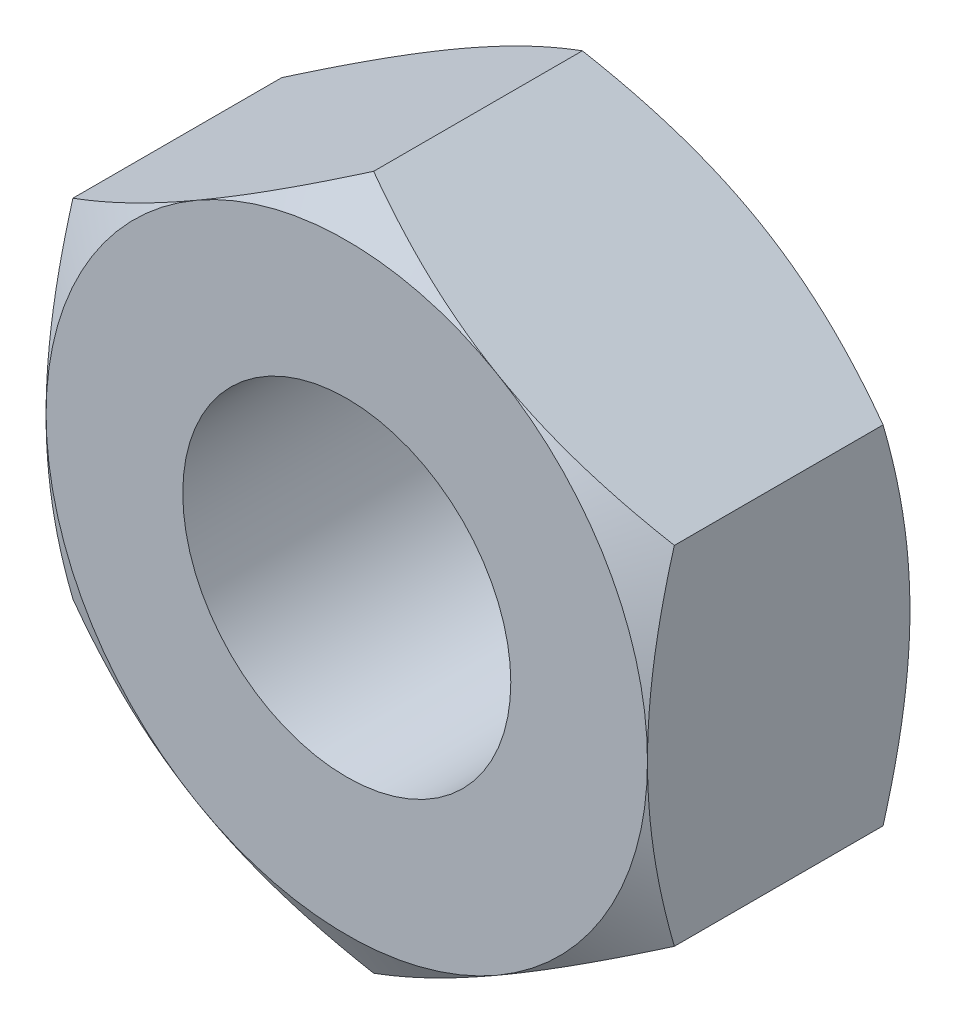
SolidWorks part; units mm, degrees
material "AISI 304"
ref_plane "Front" through (0, 0, 0) normal (0, 0, 1) x (1, 0, 0)
ref_plane "Top" through (0, 0, 0) normal (0, 1, 0) x (1, 0, 0)
ref_plane "Right" through (0, 0, 0) normal (1, 0, 0) x (0, 0, -1)
sketch "Sketch1" plane through (0, 0, 0) normal (0, 0, 1) x (1, 0, 0)
  line L1 (-2.75, 1.5877) -> (-2.75, -1.5877)
  line L2 (-2.75, -1.5877) -> (0, -3.1754)
  line L3 (0, -3.1754) -> (2.75, -1.5877)
  line L4 (2.75, -1.5877) -> (2.75, 1.5877)
  line L5 (2.75, 1.5877) -> (0, 3.1754)
  line L6 (0, 3.1754) -> (-2.75, 1.5877)
  circle A0 centre (0, 0) radius 2.75 construction
  circle A1 centre (0, 0) radius 1.5 construction
  point P10 (0, 1.5)
  dimension "hex" = 5.5
  dimension "dia" = 3
extrude "Extrude1" add sketch "Sketch1" along normal mid plane 2.4
sketch "Sketch4" plane through (0, 0, -1.2) normal (0, 0, -1) x (-1, 0, 0)
  circle A0 centre (0, 0) radius 1.5 construction
  circle A1 centre (0, 0) radius 1.5
sketch "Sketch10" plane through (0, 0, 1.2) normal (0, 0, 1) x (1, 0, 0)
  circle A0 centre (0, 0) radius 1.5 construction
  circle A1 centre (0, 0) radius 1.5
extrude "Cut-Extrude2" cut sketch "Sketch10" against normal through all draft 45
sketch "Sketch11" plane through (0, 0, -1.2) normal (0, 0, -1) x (-1, 0, 0)
  circle A0 centre (0, 0) radius 1.5 construction
  circle A1 centre (0, 0) radius 1.5
extrude "Cut-Extrude3" cut sketch "Sketch11" against normal through all draft 45
sketch "Sketch13" plane through (0, 0, -1.2) normal (0, 0, -1) x (-1, 0, 0)
  circle A0 centre (0, 0) radius 1.5 construction
  circle A1 centre (0, 0) radius 1.5
extrude "Boss-Extrude1" add sketch "Sketch13" against normal up to vertex (2.4 mm away) separate body up to point (-2.75, 1.5877, 1.2)
curve "Helix/Spiral3" pitch 0.5 height 2.4 turns 4.8
sketch "Sketch12" plane through (0, 0, 0) normal (1, 0, 0) x (0, 0, -1)
  line L0 (1.6375, 1.5) -> (1.2, 1.5)
  line L1 (1.6375, 1.5) -> (1.45, 1.1752)
  line L2 (1.45, 1.1752) -> (1.3875, 1.1752)
  line L3 (1.3875, 1.1752) -> (1.2, 1.5)
  line L4 (1.4187, 1.1752) -> (1.4187, 1.5) construction
  line L5 (1.2937, 1.3376) -> (1.5437, 1.3376) construction
  dimension "D1" = 60
  dimension "D2" = 0.0625
  dimension "D3" = 0.25
sweep "Cut-Sweep1" [suppressed] cut profiles "Sketch12" path "Helix/Spiral3"
combine bodies "Combine1" operation type subtract main body 116 bodies to subtract 117
sketch "Sketch7" plane through (0, 0, 1.2) normal (0, 0, 1) x (1, 0, 0)
  circle A0 centre (0, 0) radius 2.75 construction
  circle A1 centre (0, 0) radius 2.75
extrude "Extrude2" cut sketch "Sketch7" against normal blind 25.4 draft 60 flip side to cut
mirror "Mirror2" about plane through (0, 0, 0) normal (0, 0, 1) of "Extrude2"
sketch "Sketch8" plane through (0, 0, 1.2) normal (0, 0, 1) x (1, 0, 0)
  line L0 (-1.0607, 1.0607) -> (0, 0) construction
  line L1 (0, -1.5313) -> (0, 1.5313) construction
  circle A1 centre (0, 0) radius 1.5 construction
  point P0 (-1.0607, 1.0607)
  dimension "D1" = 45
sketch "Sketch14" plane through (0, 0, 1.2) normal (0, 0, 1) x (1, 0, 0)
  line L0 (0, 0) -> (-1.5, 0) construction
  circle A0 centre (0, 0) radius 1.5 construction
equation "\"D3@Helix/Spiral3\" = \"length@Extrude1\" "
equation "\"D2@Sketch12\" = \"D4@Helix/Spiral3\"*.125"
equation "\"D3@Sketch12\" = \"D4@Helix/Spiral3\"*.50"
